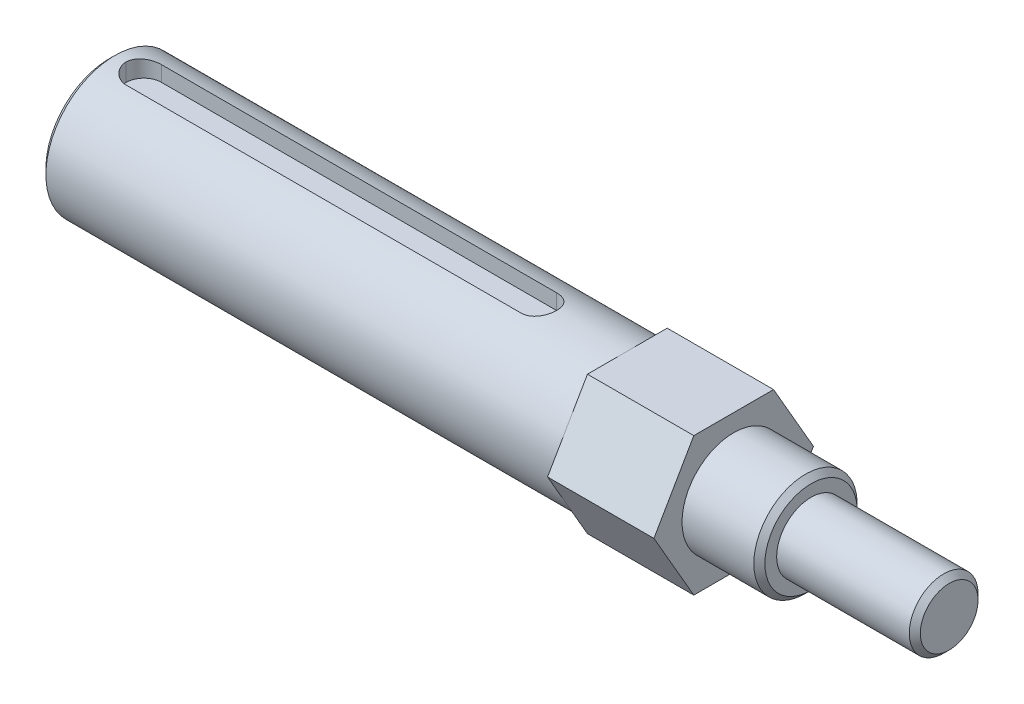
SolidWorks part; units mm, degrees
material "AISI 4130 Steel, annealed at 865C"
ref_plane "Front Plane" through (0, 0, 0) normal (0, 0, 1) x (1, 0, 0)
ref_plane "Top Plane" through (0, 0, 0) normal (0, 1, 0) x (1, 0, 0)
ref_plane "Right Plane" through (0, 0, 0) normal (1, 0, 0) x (0, 0, -1)
sketch "Sketch1" plane through (0, 0, 0) normal (0, 0, 1) x (1, 0, 0)
  line L0 (-77.8967, 0) -> (77.8967, 0) construction
  line L1 (-60.8076, 2.4879) -> (-60.8076, 6.3373)
  line L2 (-60.8076, 6.3373) -> (-3.4036, 6.3373)
  line L3 (-3.4036, 4.7498) -> (-3.4036, 6.3373)
  line L4 (16.4084, 0) -> (-43.4377, 0)
  line L11 (-3.4036, 4.7498) -> (3.7084, 4.7498)
  line L12 (3.7084, 4.7498) -> (3.7084, 3.1622)
  line L13 (3.7084, 3.1622) -> (16.4084, 3.1622)
  line L14 (16.4084, 3.1622) -> (16.4084, 0)
  line L15 (-60.8076, 2.4879) -> (-44.9326, 2.4879)
  line L16 (-44.9326, 2.4879) -> (-43.4377, 0)
  dimension "D1" = 12.6746
  dimension "D2" = 4.9759
  dimension "D3" = 15.875
  dimension "D4" = 59
  dimension "D5" = 57.404
  dimension "D6" = 16.4084
  dimension "D10" = 9.4996
  dimension "D11" = 7.112
  dimension "D12" = 6.3243
  dimension "D13" = 12.7
revolve "Revolve1" add sketch "Sketch1" angle 360 about L0
cosmetic thread "Cosmetic Thread1" parameters "D1"=15.24, "D2"=6.096
sketch "Sketch2" plane through (-3.4036, 0, 0) normal (1, 0, 0) x (0, 0, -1)
  line L0 (0, 0) -> (7.3323, 0) construction
  line L1 (-7.3323, 0) -> (-3.6662, -6.35)
  line L8 (-3.6662, -6.35) -> (3.6662, -6.35)
  line L9 (3.6662, -6.35) -> (7.3323, 0)
  line L10 (7.3323, 0) -> (3.6662, 6.35)
  line L11 (3.6662, 6.35) -> (-3.6662, 6.35)
  line L12 (-3.6662, 6.35) -> (-7.3323, 0)
  circle A0 centre (0, 0) radius 6.35 construction
  dimension "D1" = 12.7
extrude "Extrude1" add sketch "Sketch2" against normal blind 9.779
sketch "Sketch4" plane through (-60.8076, 0, 0) normal (-1, 0, 0) x (0, 0, 1)
  line L0 (0, 6.3373) -> (0, -6.7832) construction
  line L1 (-9.2385, 0) -> (8.9252, 0) construction
  line L2 (-1.6256, 6.1253) -> (-1.6256, 4.7117)
  line L3 (-1.6256, 4.7117) -> (1.6256, 4.7117)
  line L4 (1.6256, 4.7117) -> (1.6256, 6.1253)
  circle A0 centre (0, 0) radius 6.3373 construction
  circle A2 centre (0, 0) radius 6.3373 construction
  arc A3 (1.6256, 6.1253) -> (-1.6256, 6.1253) centre (0, 0) ccw
  dimension "D2" = 1.6256
  dimension "D3" = 3.2512
  dimension "D1" = 4.7117
extrude "Extrude3" cut sketch "Sketch4" against normal blind 39.5732 from offset 1.5494
fillet "Fillet1" radius 1.6256 4 edges at (-19.685, 5.4185, 1.6256) (-19.685, 5.4185, -1.6256) (-59.2582, 5.4185, 1.6256) (-59.2582, 5.4185, -1.6256)
chamfer "Chamfer1" distance 0.5081 angle 45 3 edges at (-60.8076, 0, 6.3373) (16.4084, 0, 3.1622) (3.7084, 0, 4.7498)
